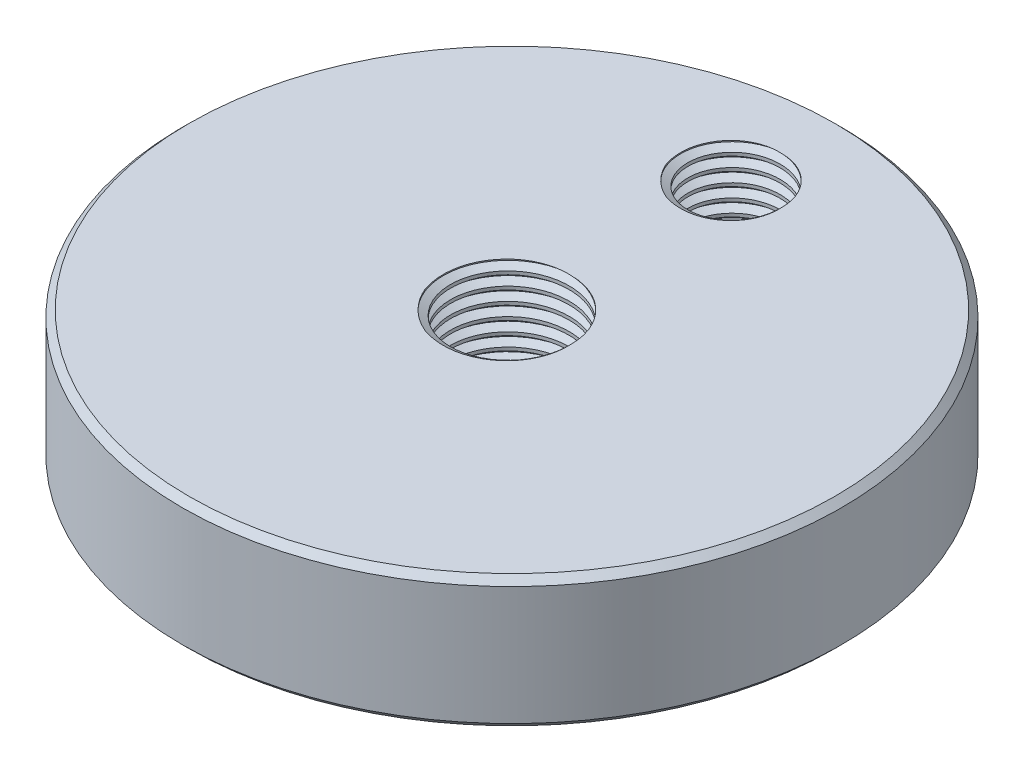
SolidWorks part; units mm, degrees
ref_plane "Front Plane" through (0, 0, 0) normal (0, 0, 1) x (1, 0, 0)
ref_plane "Top Plane" through (0, 0, 0) normal (0, 1, 0) x (1, 0, 0)
ref_plane "Right Plane" through (0, 0, 0) normal (1, 0, 0) x (0, 0, -1)
sketch "Sketch1" plane through (0, 0, 0) normal (0, 1, 0) x (1, 0, 0)
  circle A0 centre (0, 0) radius 25
  dimension "D1" = 50
extrude "Boss-Extrude1" add sketch "Sketch1" along normal blind 10
hole_wizard "Tap Drill for M10x1.0 Tap1" positions "Sketch5" profile "Sketch4" hole size "M10x1.0" standard "ISO"
sketch "Sketch5" plane through (0, 0, 0) normal (0, -1, 0) x (-1, 0, 0)
  point P0 (0, 0)
sketch "Sketch4" plane through (0, 0, 0) normal (1, 0, 0) x (0, 0, -1)
  line L0 (0, 0) -> (0, 12.7039)
  line L1 (0, 12.7039) -> (4.5, 10)
  line L2 (4.5, 10) -> (4.5, 0)
  line L5 (4.5, 0) -> (0, 0)
  line L10 (0, 12.7039) -> (-4.5, 10) construction
  line L11 (0, -6.35) -> (0, 107.95) construction
  dimension "Hole Dia." = 9
  dimension "Hole Depth" = 10
  dimension "Drill Angle" = 118
thread "Thread1" pitch 1 method cut profile "Thread Profile2" start angle 0, offset 1, length 0, pitch 1, diameter 9
ref_plane "Plane2" through (4.5, -1, 0) normal (0, 0, 1) x (1, 0, 0)
sketch "Thread Profile2" plane through (4.5, -1, 0) normal (0, 0, 1) x (1, 0, 0)
  line L0 (0, 0) -> (0, 1) construction
  line L1 (0, 0) -> (0.5413, 0.3125)
  line L2 (0.5413, 0.3125) -> (0.5413, 0.4375)
  line L3 (0.5413, 0.4375) -> (0, 0.75)
  line L4 (0.5413, 0.375) -> (0, 0.375) construction
  line L11 (0, 0) -> (0, 0.75)
  point P2 (0, 0)
  dimension "Pitch" = 1
  dimension "Profile_Angle" = 60
  dimension "Profile_Land" = 0.125
  dimension "Profile_Height" = 0.5413
sketch "Sketch10" plane through (0, 0, 0) normal (0, 1, 0) x (1, 0, 0)
  point P0 (0, 17)
  dimension "D1" = 17
hole_wizard "Tap Drill for M8x1.0 Tap1" positions "Sketch12" profile "Sketch11" hole size "M8x1.0" standard "ISO"
sketch "Sketch12" plane through (0, 0, 0) normal (0, -1, 0) x (-1, 0, 0)
  point P6 (0, 17)
sketch "Sketch11" plane through (0, 0, -17) normal (1, 0, 0) x (0, 0, -1)
  line L0 (0, 0) -> (0, 12.103)
  line L1 (0, 12.103) -> (3.5, 10)
  line L2 (3.5, 10) -> (3.5, 0)
  line L5 (3.5, 0) -> (0, 0)
  line L10 (0, 12.103) -> (-3.5, 10) construction
  line L11 (0, -6.35) -> (0, 107.95) construction
  dimension "Hole Dia." = 7
  dimension "Hole Depth" = 10
  dimension "Drill Angle" = 118
thread "Thread2" pitch 1 method cut profile "Thread Profile3" start angle 0, offset 1, length 0, pitch 1, diameter 7
ref_plane "Plane3" through (3.5, -1, -17) normal (0, 0, 1) x (1, 0, 0)
sketch "Thread Profile3" plane through (3.5, -1, -17) normal (0, 0, 1) x (1, 0, 0)
  line L0 (0, 0) -> (0, 1) construction
  line L1 (0, 0) -> (0.5413, 0.3125)
  line L2 (0.5413, 0.3125) -> (0.5413, 0.4375)
  line L3 (0.5413, 0.4375) -> (0, 0.75)
  line L4 (0.5413, 0.375) -> (0, 0.375) construction
  line L11 (0, 0) -> (0, 0.75)
  point P2 (0, 0)
  dimension "Pitch" = 1
  dimension "Profile_Angle" = 60
  dimension "Profile_Land" = 0.125
  dimension "Profile_Height" = 0.5413
chamfer "Chamfer1" distance 0.5 angle 45 2 edges at (0, 10, 25) (0, 0, 25)
